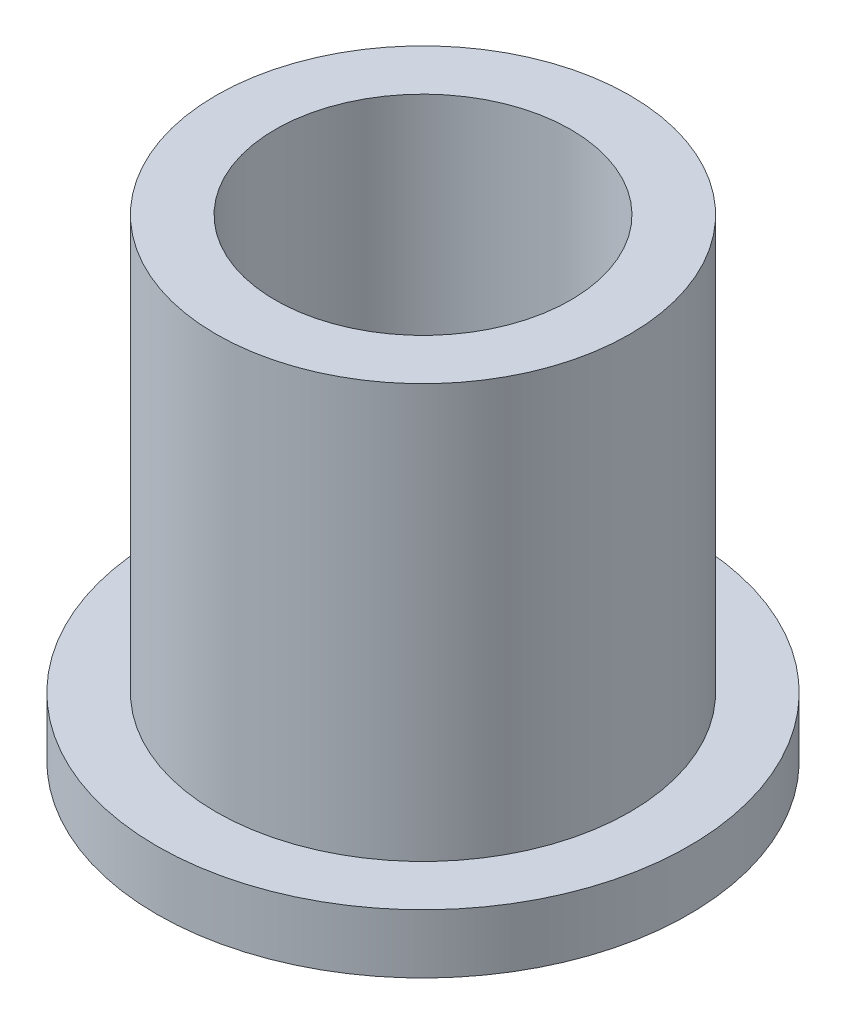
SolidWorks part; units mm, degrees
material "Brass"
ref_plane "Front Plane" through (0, 0, 0) normal (0, 0, 1) x (1, 0, 0)
ref_plane "Top Plane" through (0, 0, 0) normal (0, 1, 0) x (1, 0, 0)
ref_plane "Right Plane" through (0, 0, 0) normal (1, 0, 0) x (0, 0, -1)
sketch "Sketch1" plane through (0, 0, 0) normal (0, 0, 1) x (1, 0, 0)
  line L0 (3.9688, 0) -> (7.1437, 0)
  line L1 (7.1437, 0) -> (7.1437, 1.5875)
  line L2 (7.1437, 1.5875) -> (5.5562, 1.5875)
  line L3 (5.5562, 1.5875) -> (5.5562, 12.7)
  line L4 (5.5562, 12.7) -> (3.9687, 12.7)
  line L5 (3.9687, 12.7) -> (3.9688, 0)
  line L6 (0, 0) -> (0, 40.9931) construction
  dimension "D1" = 7.9375
  dimension "D2" = 11.1125
  dimension "D3" = 14.2875
  dimension "D4" = 1.5875
  dimension "D5" = 12.7
revolve "Revolve1" add sketch "Sketch1" angle 360 about L6
